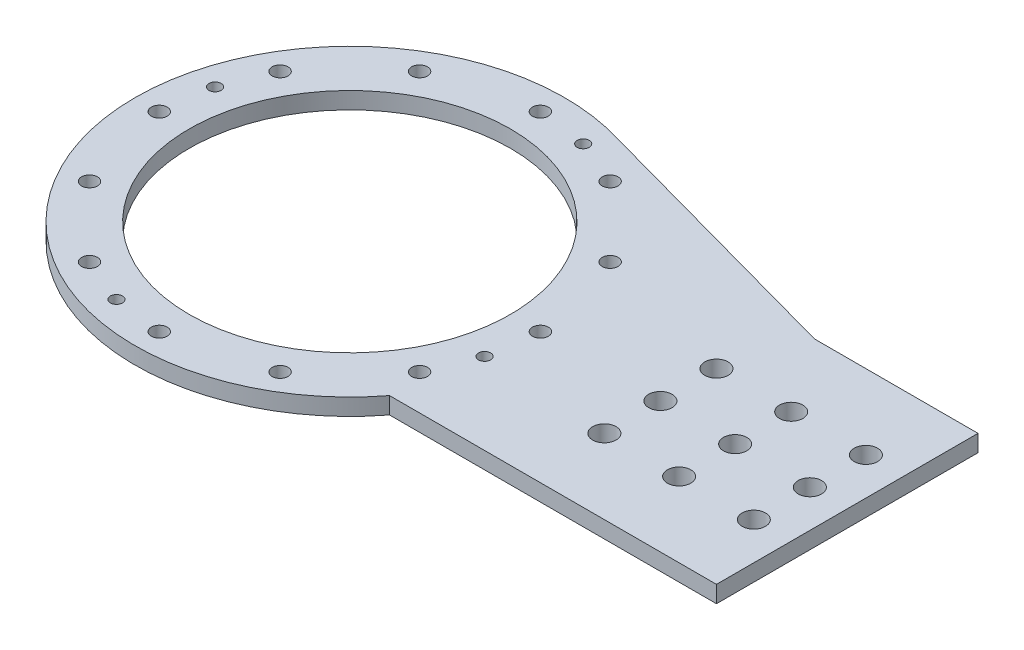
SolidWorks part; units mm, degrees
ref_plane "Front Plane" through (0, 0, 0) normal (0, 0, 1) x (1, 0, 0)
ref_plane "Top Plane" through (0, 0, 0) normal (0, 1, 0) x (1, 0, 0)
ref_plane "Right Plane" through (0, 0, 0) normal (1, 0, 0) x (0, 0, -1)
sketch "Sketch1" plane through (0, 0, 0) normal (0, 1, 0) x (1, 0, 0)
  circle A0 centre (0, 0) radius 57.5
  dimension "D1" = 115
extrude "Boss-Extrude1" add sketch "Sketch1" along normal blind 4.5
sketch "Sketch2" plane through (0, 0, 0) normal (0, 1, 0) x (1, 0, 0)
  line L0 (133.1258, 35) -> (-6.8742, 35)
  line L1 (133.1258, 35) -> (133.1258, -35)
  line L2 (-6.8742, 35) -> (-6.8742, -35)
  line L3 (133.1258, -35) -> (-6.8742, -35)
  line L4 (-6.8742, 0) -> (133.1258, 0) construction
  line L5 (63.1258, 35) -> (63.1258, -35) construction
  point P1 (63.1258, 0)
  dimension "D1" = 70
  dimension "D2" = 140
extrude "Boss-Extrude2" add sketch "Sketch2" along normal blind 4.5
sketch "Sketch3" plane through (0, 0, 0) normal (0, 1, 0) x (1, 0, 0)
  line L0 (89.3733, 35) -> (13.7685, 55.8272)
  line L1 (133.1258, 35) -> (45.6207, 35) construction
  line L2 (13.7685, 55.8272) -> (13.7685, 13.5588)
  line L3 (13.7685, 13.5588) -> (89.3733, 35)
  circle A0 centre (0, 0) radius 57.5 construction
extrude "Boss-Extrude3" add sketch "Sketch3" along normal blind 4.5
mirror "Mirror1" [suppressed] about plane through (0, 0, 0) normal (0, 0, 1)
sketch "Sketch4" plane through (0, 4.5, 0) normal (0, 1, 0) x (1, 0, 0)
  circle A0 centre (0, 0) radius 43
  dimension "D1" = 86
extrude "Cut-Extrude1" cut sketch "Sketch4" against normal through all
sketch "Sketch7" plane through (0, 4.5, 0) normal (0, 1, 0) x (1, 0, 0)
  line L0 (0, 0) -> (133.1258, 0) construction
  line L1 (133.1258, -35) -> (133.1258, 35) construction
  line L2 (123.1258, 15) -> (123.1258, -15) construction
  circle A0 centre (123.1258, 15) radius 3.125
  circle A1 centre (123.1258, -15) radius 3.125
  point P8 (123.1258, 0)
  dimension "D1" = 6.25
  dimension "D2" = 30
  dimension "D3" = 10
extrude "Cut-Extrude8" cut sketch "Sketch7" against normal through all
pattern_linear "LPattern1" count 3 spacing 20 along (-1, 0, 0) of "Cut-Extrude8"
sketch "Sketch5" plane through (0, 0, 0) normal (0, 1, 0) x (1, 0, 0)
  circle A0 centre (0, 0) radius 51 construction
  circle A1 centre (-51, 0) radius 2.125
  dimension "D1" = 4.25
  dimension "D2" = 102
extrude "Cut-Extrude5" cut sketch "Sketch5" against normal through all and the other way through all contours A1 region at (-51, 0, 0)
pattern_circular "CirPattern1" count 12 over 360 about axis through (0, 4.5, 0) along (0, 1, 0) of "Cut-Extrude5"
sketch "Sketch11" plane through (0, 4.5, 0) normal (0, 1, 0) x (1, 0, 0)
  line L0 (52.9426, -35) -> (62.7348, -25.9656)
  line L1 (45.6207, -35) -> (133.1258, -35) construction
  line L2 (62.7348, -25.9656) -> (71.0702, -35)
  line L3 (71.0702, -35) -> (52.9426, -35)
extrude "Cut-Extrude16" [suppressed] cut sketch "Sketch11" against normal through all
sketch "Sketch12" plane through (0, 4.5, 0) normal (0, 1, 0) x (1, 0, 0)
  line L0 (0, 0) -> (-51, 0) construction
  line L1 (0, 0) -> (-49.2622, 13.1998) construction
  circle A0 centre (0, 0) radius 51 construction
  circle A1 centre (-49.2622, 13.1998) radius 1.625
  dimension "D1" = 102
  dimension "D2" = 3.25
  dimension "D3" = 15
extrude "Cut-Extrude17" cut sketch "Sketch12" against normal through all
pattern_circular "CirPattern2" count 4 over 360 about axis through (0, 4.5, 0) along (0, 1, 0) of "Cut-Extrude17"
sketch "Sketch13" plane through (0, 4.5, 0) normal (0, 1, 0) x (1, 0, 0)
  line L0 (133.1258, 0) -> (0, 0) construction
  line L1 (133.1258, -35) -> (133.1258, 35) construction
  circle A0 centre (123.1258, 0) radius 3.125
  dimension "D1" = 6.25
  dimension "D2" = 10
extrude "Cut-Extrude18" cut sketch "Sketch13" against normal blind 10 contours A0
pattern_linear "LPattern2" count 3 spacing 20 along (-1, 0, 0) of "Cut-Extrude18"
